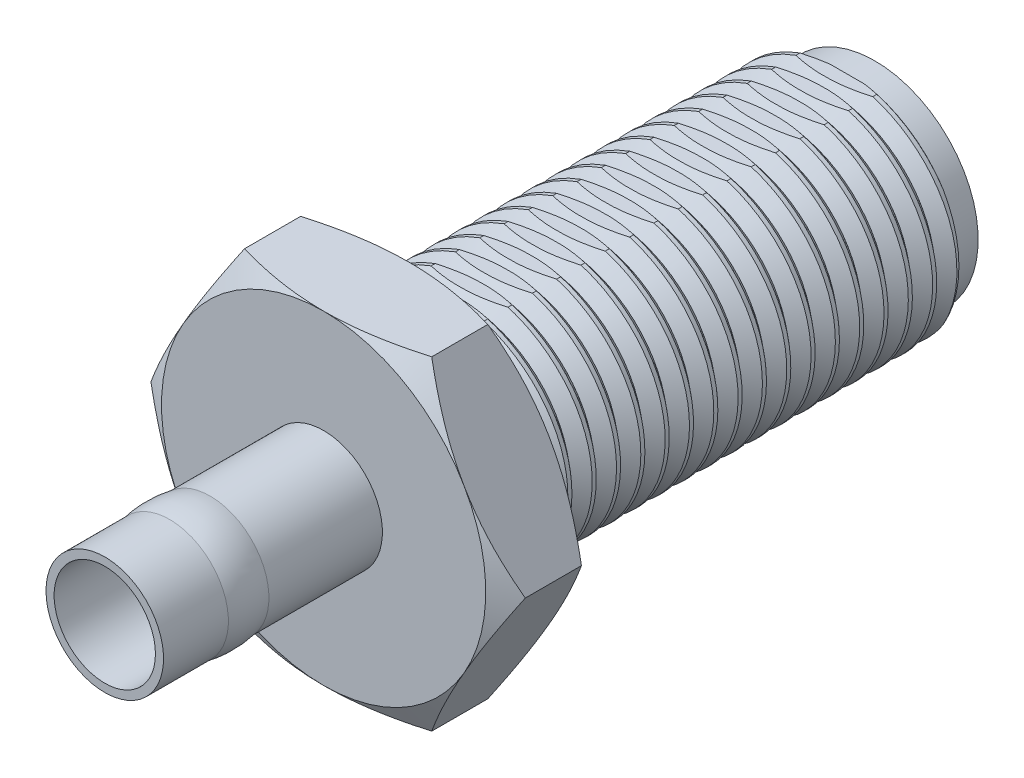
SolidWorks part; units mm, degrees
note: The reader was unsure of these and kept them because the rebuilt part matched: shared geometry of "Sketch6<2>".
material "Brass"
ref_plane "Front Plane" through (0, 0, 0) normal (0, 0, 1) x (1, 0, 0)
ref_plane "Top Plane" through (0, 0, 0) normal (0, 1, 0) x (1, 0, 0)
ref_plane "Right Plane" through (0, 0, 0) normal (1, 0, 0) x (0, 0, -1)
sketch "Sketch1" plane through (0, 0, 0) normal (1, 0, 0) x (0, 0, -1)
  line L0 (0, 0) -> (0, 1.45)
  line L1 (0, 1.45) -> (1.6, 1.45)
  line L2 (2.6, 1.45) -> (5.4, 1.45)
  line L3 (5.4, 1.45) -> (5.4, 4)
  line L4 (5.4, 4) -> (7.5, 4)
  line L5 (7.5, 4) -> (7.5, 2.875)
  line L6 (7.5, 2.875) -> (18.2, 2.875)
  line L7 (18.2, 2.875) -> (18.2, 2.55)
  line L8 (18.2, 2.55) -> (19, 2.55)
  line L9 (19, 2.55) -> (19, 0)
  line L10 (19, 0) -> (0, 0) construction
  line L11 (0, 0) -> (19, 0)
  arc A0 (1.6, 1.45) -> (2.6, 1.45) centre (2.1, -1.025) cw
  dimension "D1" = 8
  dimension "D10" = 3
  dimension "D2" = 2.1
  dimension "D3" = 13.6
  dimension "D4" = 5.1
  dimension "D5" = 0.8
  dimension "D6" = 5.75
  dimension "D7" = 5.4
  dimension "D8" = 2.9
  dimension "D9" = 1
  dimension "D11" = 1.6
revolve "Revolve1" add sketch "Sketch1" angle 360 about L10
sketch "Sketch2" plane through (0, 0, -7.5) normal (0, 0, -1) x (-1, 0, 0)
  line L1 (2.3094, 4) -> (-2.3094, 4)
  line L2 (-2.3094, 4) -> (-4.6188, 0)
  line L3 (-4.6188, 0) -> (-2.3094, -4)
  line L4 (-2.3094, -4) -> (2.3094, -4)
  line L5 (2.3094, -4) -> (4.6188, 0)
  line L6 (4.6188, 0) -> (2.3094, 4)
  circle A0 centre (0, 0) radius 4 construction
  circle A1 centre (0, 0) radius 4 construction
extrude "Boss-Extrude1" add sketch "Sketch2" against normal up to surface (2.1 mm away) up to face at (-1.45, 0, -5.4)
sketch "Sketch3" plane through (0, 0, 0) normal (1, 0, 0) x (0, 0, -1)
  line L0 (4.8226, 3) -> (4.8226, 5.7321)
  line L1 (4.8226, 5.7321) -> (6.4, 5.7321)
  line L2 (6.4, 5.7321) -> (4.8226, 3)
  line L3 (5.4, 0) -> (7.5, 0) construction
  line L4 (7.5, -2.875) -> (7.5, 2.875) construction
  line L5 (6.45, 4) -> (6.45, 0) construction
  line L6 (5.4, 4) -> (7.5, 4) construction
  line L7 (6.5, 5.7321) -> (8.0774, 3)
  line L8 (8.0774, 5.7321) -> (6.5, 5.7321)
  line L9 (8.0774, 3) -> (8.0774, 5.7321)
  dimension "D1" = 30
  dimension "D2" = 0.1
  dimension "D3" = 1
revolve "Cut-Revolve1" cut sketch "Sketch3" angle 360 about L3
sketch "Sketch5" plane through (0, 0, -19) normal (0, 0, -1) x (-1, 0, 0)
  circle A2 centre (0, 0) radius 2.35
  circle A3 centre (0, 0) radius 2.35
  dimension "D1" = 0.2
extrude "Cut-Extrude2" cut sketch "Sketch5" against normal blind 1.95
sketch "Sketch6" plane through (0, 0, -17.05) normal (0, 0, -1) x (-1, 0, 0)
  circle A0 centre (0, 0) radius 0.3
  circle A1 centre (0, 0) radius 0.4
  dimension "D1" = 0.6
  dimension "D2" = 0.1
extrude "Boss-Extrude2" add sketch "Sketch6" along normal blind 0.1
extrude "Cut-Extrude3" cut sketch "Sketch6<2>" against normal through all contours A0
sketch "Sketch6<2>" plane through (0, 0, -17.05) normal (0, 0, -1) x (-1, 0, 0) same geometry as "Sketch6"
sketch "Sketch8" plane through (0, 0, -18.2) normal (0, 0, -1) x (-1, 0, 0)
  circle A0 centre (0, 0) radius 2.875 construction
  circle A1 centre (0, 0) radius 2.875
curve "Helix/Spiral1" pitch 0.6 height 10.2 turns 17
sketch "Sketch9" plane through (0, 0, 0) normal (0, 1, 0) x (1, 0, 0)
  line L0 (-2.875, 8.25) -> (-2.875, 7.75)
  line L1 (-2.875, 18.2) -> (-2.875, 7.5) construction
  line L2 (-2.875, 7.75) -> (-2.575, 8)
  line L3 (-2.575, 8) -> (-2.875, 8.25)
  line L4 (-2.575, 8) -> (-2.875, 8) construction
  dimension "D1" = 0.5
  dimension "D2" = 0.3
sweep "Cut-Sweep1" cut profiles "Sketch9" path "Helix/Spiral1"
sketch "Sketch10" plane through (0, 0, 0) normal (0, 0, 1) x (1, 0, 0)
  circle A2 centre (0, 0) radius 1.25
  circle A3 centre (0, 0) radius 1.25
  dimension "D1" = 0.2
extrude "Cut-Extrude4" cut sketch "Sketch10" against normal up to surface (5.4 mm away) up to face at (-1.45, 0, -5.4)
sketch "Sketch4" plane through (0, 0, -18.2) normal (0, 0, -1) x (-1, 0, 0)
  line L0 (-0.9165, 2.725) -> (0.9165, 2.725)
  circle A0 centre (0, 0) radius 2.875 construction
  arc A1 (0.9165, 2.725) -> (-0.9165, 2.725) centre (0, 0) ccw
  dimension "D1" = 5.6
extrude "Cut-Extrude1" cut sketch "Sketch4" against normal up to surface (10.7 mm away) up to face at (-2.875, 0, -7.5)
equation "\"panjang\"= 120"
equation "\"lebar\"=40"
equation "\"tinggi\"=10"
